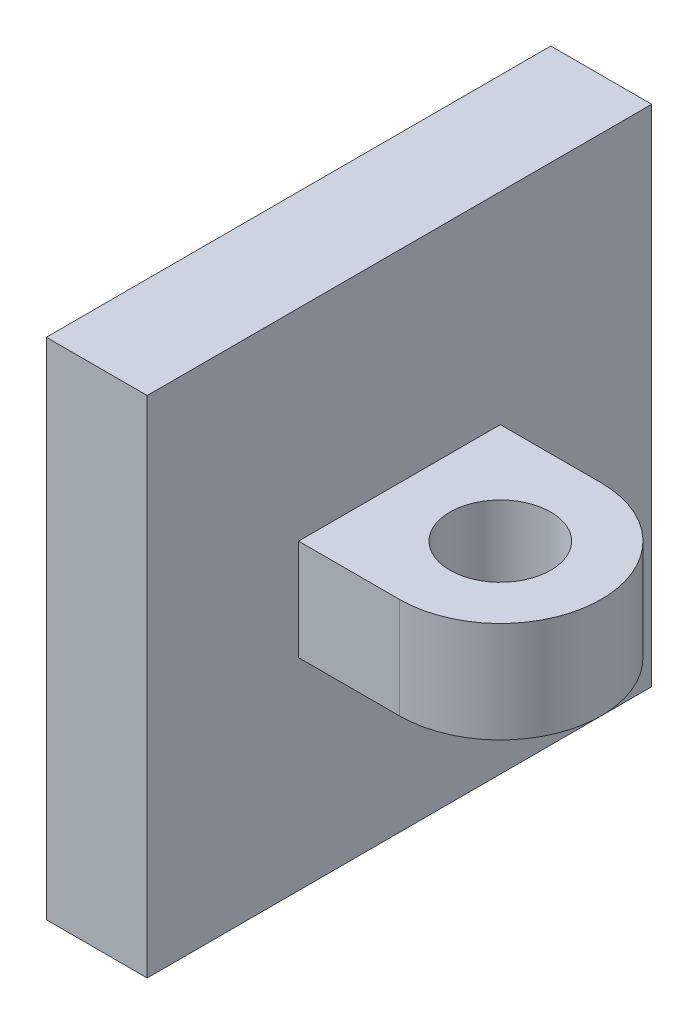
SolidWorks part; units mm, degrees
ref_plane "Front Plane" through (0, 0, 0) normal (0, 0, 1) x (1, 0, 0)
ref_plane "Top Plane" through (0, 0, 0) normal (0, 1, 0) x (1, 0, 0)
ref_plane "Right Plane" through (0, 0, 0) normal (1, 0, 0) x (0, 0, -1)
sketch "Sketch1" plane through (0, 0, 0) normal (0, 1, 0) x (1, 0, 0)
  line L1 (-0.7701, 1.6207) -> (1.2299, 1.6207)
  line L2 (-0.7701, 1.6207) -> (-0.7701, -8.3793)
  line L3 (-0.7701, -8.3793) -> (1.2299, -8.3793)
  line L4 (1.2299, 1.6207) -> (1.2299, -8.3793)
  dimension "D1" = 2
  dimension "D2" = 10
extrude "Boss-Extrude1" add sketch "Sketch1" along normal blind 10
sketch "Sketch2" plane through (1.2299, 0, 0) normal (1, 0, 0) x (0, 0, -1)
  line L0 (-8.3793, 10) -> (1.6207, 0)
  line L2 (-5.3793, 4) -> (-1.3793, 4)
  line L3 (-5.3793, 4) -> (-5.3793, 6)
  line L4 (-5.3793, 6) -> (-1.3793, 6)
  line L5 (-1.3793, 4) -> (-1.3793, 6)
  line L6 (-5.3793, 4) -> (-1.3793, 6) construction
  line L7 (-5.3793, 6) -> (-1.3793, 4) construction
  point P4 (-3.3793, 5)
  dimension "D1" = 4
  dimension "D2" = 2
extrude "Boss-Extrude2" add sketch "Sketch2" along normal blind 5 contours L4 L3 L2 L0 | L2 L5 L4 L0 region at (1.2299, 5.1667, 2.4626) region at (1.2299, 4.8333, 4.296)
sketch "Sketch3" plane through (0, 6, 0) normal (0, 1, 0) x (1, 0, 0)
  line L0 (6.2299, -3.3793) -> (3.2299, -3.3793)
  line L1 (6.2299, -5.3793) -> (6.2299, -1.3793) construction
  line L2 (6.2299, -1.3793) -> (1.2299, -1.3793) construction
  line L3 (6.2299, -5.3793) -> (1.2299, -5.3793) construction
  line L4 (3.2299, -1.3793) -> (6.2299, -1.3793)
  line L5 (6.2299, -1.3793) -> (6.2299, -5.3793)
  line L6 (6.2299, -5.3793) -> (3.2299, -5.3793)
  circle A0 centre (3.2299, -3.3793) radius 1
  arc A1 (3.2299, -1.3793) -> (3.2299, -5.3793) centre (3.2299, -3.3793) cw
  line M3 (1.2299, -5.3793) -> (6.2299, -5.3793)
  line M4 (6.2299, -5.3793) -> (6.2299, -1.3793)
  line M5 (6.2299, -1.3793) -> (1.2299, -1.3793)
extrude "Cut-Extrude1" cut sketch "Sketch3" against normal blind 15 contours A0 | A1 L0 M5 M4 | L0 A1 M3 M4 region at (5.4456, 6, 4.5455) region at (5.4456, 6, 2.2132) region at (2.2582, 6, 3.3793)
